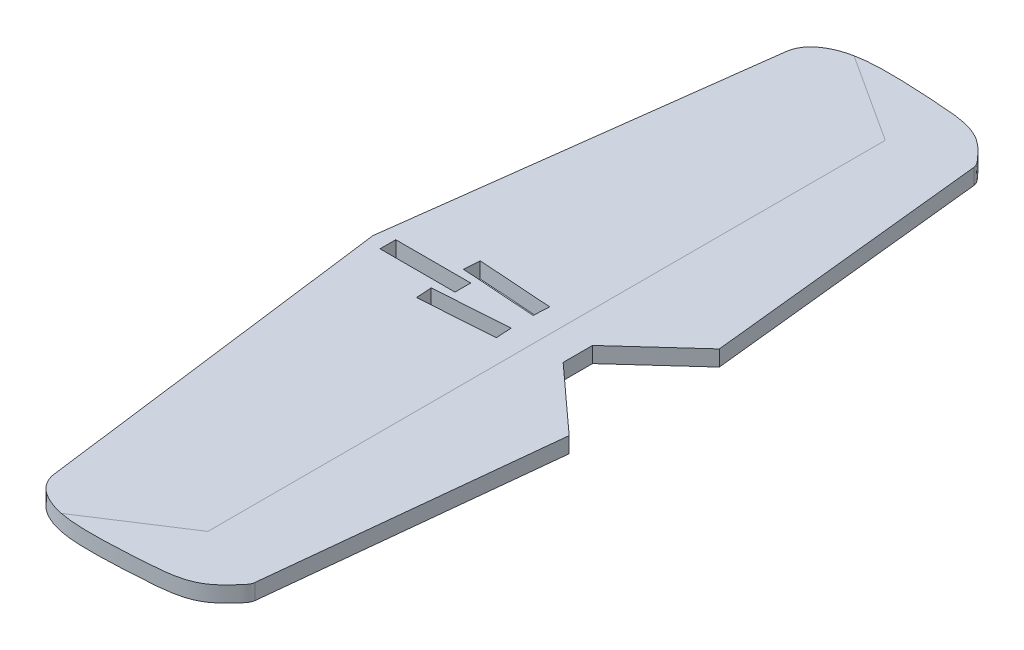
SolidWorks part; units mm, degrees
ref_plane "Front" through (0, 0, 0) normal (0, 0, 1) x (1, 0, 0)
ref_plane "Top" through (0, 0, 0) normal (0, 1, 0) x (1, 0, 0)
ref_plane "Right" through (0, 0, 0) normal (1, 0, 0) x (0, 0, -1)
sketch "Sketch1" plane through (0, 0, 0) normal (0, 1, 0) x (1, 0, 0)
  line L0 (-176.9262, 542.9298) -> (1961.7405, 542.9298) construction
  line L1 (0, 0) -> (127.924, 0) construction
  line L2 (0, 0) -> (15.9702, 123.8881)
  line L3 (81.8051, 121.8383) -> (91.9526, 25.4423)
  line L4 (91.9526, 25.4423) -> (69.4479, 4.9835)
  line L5 (69.4479, 4.9835) -> (69.4479, -4.9835)
  line L6 (28.7279, 134.3182) -> (58.8561, 114.7867)
  line L7 (58.8561, 114.7867) -> (58.8561, -114.7867)
  line L8 (91.9526, -25.4423) -> (69.4479, -4.9835)
  line L9 (81.8051, -121.8383) -> (91.9526, -25.4423)
  line L10 (28.7279, -134.3182) -> (58.8561, -114.7867)
  line L11 (0, 0) -> (15.9702, -123.8881)
  spline S0 degree 3 poles (15.9702, 123.8881) (16.4963, 127.9695) (23.1267, 134.083) (33.9982, 135.2168) (46.0547, 135.1451) (57.8789, 134.4575) (71.9866, 133.2575) (78.6193, 126.5586) (81.6818, 123.0092) (81.8051, 121.8383) knots 0 0 0 0 0.137874 0.340707 0.419473 0.623496 0.82501 0.952424 1 1 1 1
  spline S1 degree 3 poles (15.9702, -123.8881) (16.4963, -127.9695) (23.1267, -134.083) (33.9982, -135.2168) (46.0547, -135.1451) (57.8789, -134.4575) (71.9866, -133.2575) (78.6193, -126.5586) (81.6818, -123.0092) (81.8051, -121.8383) knots 0 0 0 0 0.137874 0.340707 0.419473 0.623496 0.82501 0.952424 1 1 1 1
  point P28 (69.4479, 0)
  point P30 (58.8561, 0)
extrude "Boss-Extrude1" add sketch "Sketch1" along normal blind 5.334 contours L11 S1 L10 L7 L6 S0 L2 | L10 S1 L9 L8 L5 L4 L3 S0 L6 L7 region at (32.8687, 0, 0) region at (57.3792, 0, -131.6404)
split line "Split Line1"
sketch "Sketch1<4>" plane through (0, 0, 0) normal (0, 1, 0) x (1, 0, 0) same geometry as "Sketch1"
sketch "Sketch3" plane through (0, 5.334, 0) normal (0, 1, 0) x (1, 0, 0)
  line L8 (50.9115, 9.0447) -> (25.5717, 10.7919)
  line L9 (25.5717, 10.7919) -> (25.2048, 5.4705)
  line L10 (25.2048, 5.4705) -> (50.5446, 3.7233)
  line L11 (50.5446, 3.7233) -> (50.9115, 9.0447)
  line L12 (25.5717, -10.7919) -> (50.9115, -9.0447)
  line L13 (50.9115, -9.0447) -> (50.5446, -3.7233)
  line L14 (50.5446, -3.7233) -> (25.2048, -5.4705)
  line L15 (25.2048, -5.4705) -> (25.5717, -10.7919)
extrude "Fuselage Slots" cut sketch "Sketch3" against normal up to next
sketch "Sketch4" plane through (0, 5.334, 0) normal (0, 1, 0) x (1, 0, 0)
  line L1 (5.08, -2.667) -> (30.48, -2.667)
  line L2 (5.08, -2.667) -> (5.08, 2.667)
  line L3 (5.08, 2.667) -> (30.48, 2.667)
  line L4 (30.48, -2.667) -> (30.48, 2.667)
  line L5 (5.08, -2.667) -> (30.48, 2.667) construction
  line L6 (5.08, 2.667) -> (30.48, -2.667) construction
  point P0 (17.78, 0)
  dimension "D1" = 25.4
  dimension "D2" = 5.334
  dimension "D3" = 5.08
extrude "Rudder Slot" cut sketch "Sketch4" against normal up to next
sketch "Build Plans" [suppressed] plane through (0, 5.334, 0) normal (0, 1, 0) x (1, 0, 0)
  line L0 (81.8051, -121.8383) -> (91.9526, -25.4423) construction
  line L1 (91.9526, -25.4423) -> (69.4479, -4.9835) construction
  line L2 (69.4479, -4.9835) -> (69.4479, 4.9835) construction
  line L3 (69.4479, 4.9835) -> (91.9526, 25.4423) construction
  line L4 (91.9526, 25.4423) -> (81.8051, 121.8383) construction
  line L5 (15.9702, 123.8881) -> (0, 0) construction
  line L6 (0, 0) -> (15.9702, -123.8881) construction
  line L7 (81.8051, -121.8383) -> (91.9526, -25.4423)
  line L8 (91.9526, -25.4423) -> (69.4479, -4.9835)
  line L9 (69.4479, -4.9835) -> (69.4479, 4.9835)
  line L10 (69.4479, 4.9835) -> (91.9526, 25.4423)
  line L11 (91.9526, 25.4423) -> (81.8051, 121.8383)
  line L12 (15.9702, 123.8881) -> (0, 0)
  line L13 (0, 0) -> (15.9702, -123.8881)
  line L14 (28.7279, -134.3182) -> (58.8561, -114.7867) construction
  line L15 (58.8561, -114.7867) -> (58.8561, 114.7867) construction
  line L16 (58.8561, 114.7867) -> (28.7279, 134.3182) construction
  line L17 (28.7279, -134.3182) -> (58.8561, -114.7867)
  line L18 (58.8561, -114.7867) -> (58.8561, 114.7867)
  line L19 (58.8561, 114.7867) -> (28.7279, 134.3182)
  line L20 (50.5446, -3.7233) -> (25.2048, -5.4705) construction
  line L21 (25.2048, -5.4705) -> (25.5717, -10.7919) construction
  line L22 (25.5717, -10.7919) -> (50.9115, -9.0447) construction
  line L23 (50.9115, -9.0447) -> (50.5446, -3.7233) construction
  line L24 (50.5446, 3.7233) -> (50.9115, 9.0447) construction
  line L25 (50.9115, 9.0447) -> (25.5717, 10.7919) construction
  line L26 (25.5717, 10.7919) -> (25.2048, 5.4705) construction
  line L27 (25.2048, 5.4705) -> (50.5446, 3.7233) construction
  line L28 (5.08, 2.667) -> (5.08, -2.667) construction
  line L29 (30.48, 2.667) -> (5.08, 2.667) construction
  line L30 (30.48, -2.667) -> (30.48, 2.667) construction
  line L31 (5.08, -2.667) -> (30.48, -2.667) construction
  line L32 (50.5446, -3.7233) -> (25.2048, -5.4705)
  line L33 (25.2048, -5.4705) -> (25.5717, -10.7919)
  line L34 (25.5717, -10.7919) -> (50.9115, -9.0447)
  line L35 (50.9115, -9.0447) -> (50.5446, -3.7233)
  line L36 (50.5446, 3.7233) -> (50.9115, 9.0447)
  line L37 (50.9115, 9.0447) -> (25.5717, 10.7919)
  line L38 (25.5717, 10.7919) -> (25.2048, 5.4705)
  line L39 (25.2048, 5.4705) -> (50.5446, 3.7233)
  line L40 (5.08, 2.667) -> (5.08, -2.667)
  line L41 (30.48, 2.667) -> (5.08, 2.667)
  line L42 (30.48, -2.667) -> (30.48, 2.667)
  line L43 (5.08, -2.667) -> (30.48, -2.667)
  spline S0 degree 3 poles (911.8651, 1657.0173) (-87.6086, -86.4171) (-13.8609, -135.5015) (46.0547, -135.1451) (57.8789, -134.4575) (71.9866, -133.2575) (89.548, -115.5207) (103.1428, -92.364) (-1844.6991, 413.7988) knots -1.789838 -1.789838 -1.789838 -1.789838 0.340707 0.419473 0.623496 0.82501 0.952424 1.620368 1.620368 1.620368 1.620368 only from (28.7279, -134.3182) to (81.8051, -121.8383) construction
  spline S1 degree 3 poles (-1844.7799, -413.8198) (103.1431, 92.3635) (89.5482, 115.5206) (71.9866, 133.2575) (57.8789, 134.4575) (46.0547, 135.1451) (-13.8604, 135.5015) (-87.6072, 86.4181) (911.8351, -1656.9649) knots -0.390242 -0.390242 -0.390242 -0.390242 0.277712 0.405126 0.60664 0.810662 0.889428 3.019952 3.019952 3.019952 3.019952 only from (81.8051, 121.8383) to (28.7279, 134.3182) construction
  spline S2 degree 3 poles (-1054.8651, 1814.3624) (238.007, -70.0202) (-16.368, 290.2188) (-2.8002, 18.0012) (1742.9986, -881.2622) knots -2.312732 -2.312732 -2.312732 -2.312732 0.092262 1.447423 1.447423 1.447423 1.447423 only from (28.7279, 134.3182) to (15.9702, 123.8881) construction
  spline S3 degree 3 poles (1743.0066, 881.2663) (-2.8002, -18.0009) (-16.3681, -290.2186) (238.0062, 70.0192) (-1054.8561, -1814.3492) knots -1.217289 -1.217289 -1.217289 -1.217289 0.137874 2.542862 2.542862 2.542862 2.542862 only from (15.9702, -123.8881) to (28.7279, -134.3182) construction
  spline S4 degree 3 poles (28.7279, -134.3182) (31.4493, -134.8682) (36.2888, -135.2032) (46.0547, -135.1451) (57.8789, -134.4575) (71.9866, -133.2575) (78.6193, -126.5586) (81.6818, -123.0092) (81.8051, -121.8383) knots 0.230135 0.230135 0.230135 0.230135 0.340707 0.419473 0.623496 0.82501 0.952424 1 1 1 1
  spline S5 degree 3 poles (81.8051, 121.8383) (81.6818, 123.0092) (78.6193, 126.5586) (71.9866, 133.2575) (57.8789, 134.4575) (46.0547, 135.1451) (36.2888, 135.2032) (31.4493, 134.8682) (28.7279, 134.3182) knots 0.230135 0.230135 0.230135 0.230135 0.277712 0.405126 0.60664 0.810662 0.889428 1 1 1 1
  spline S6 degree 3 poles (28.7279, 134.3182) (26.4571, 133.8593) (20.9749, 132.0989) (16.4963, 127.9695) (15.9702, 123.8881) knots 0 0 0 0 0.092262 0.230135 0.230135 0.230135 0.230135
  spline S7 degree 3 poles (15.9702, -123.8881) (16.4963, -127.9695) (20.9749, -132.0989) (26.4571, -133.8593) (28.7279, -134.3182) knots 0 0 0 0 0.137874 0.230135 0.230135 0.230135 0.230135
